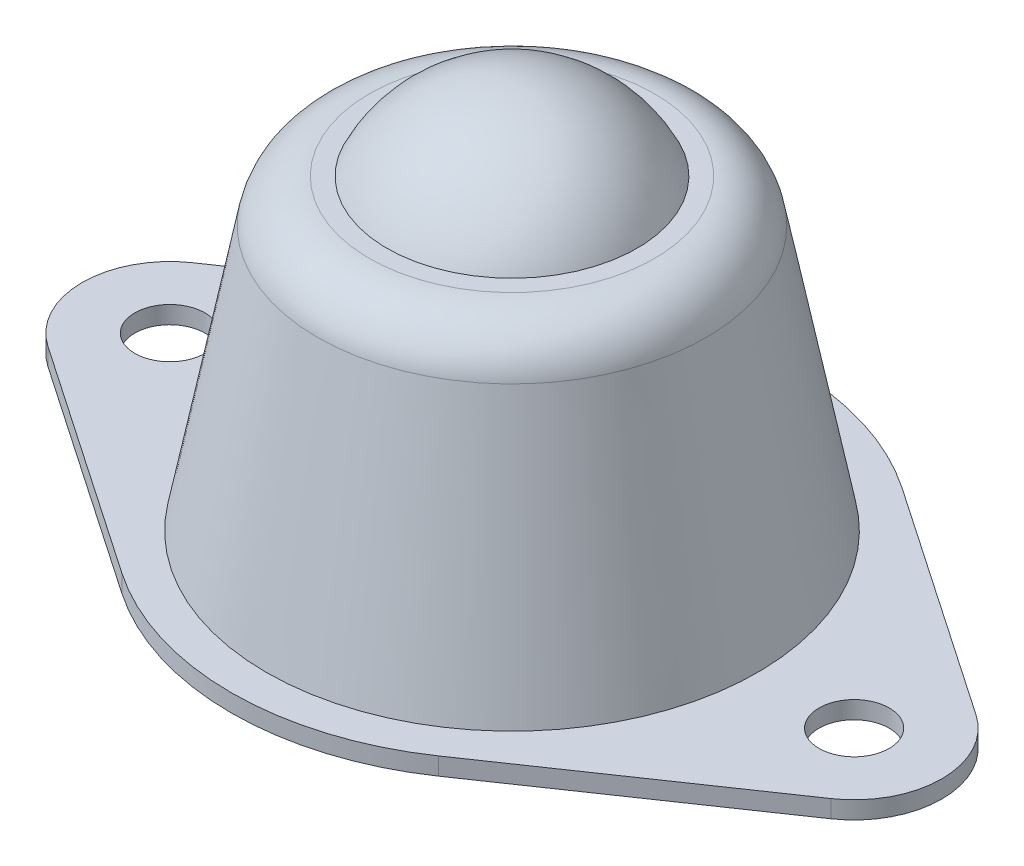
SolidWorks part; units mm, degrees
ref_plane "Front" through (0, 0, 0) normal (0, 0, 1) x (1, 0, 0)
ref_plane "Top" through (0, 0, 0) normal (0, 1, 0) x (1, 0, 0)
ref_plane "Right" through (0, 0, 0) normal (1, 0, 0) x (0, 0, -1)
sketch "草圖1" plane through (0, 0, 0) normal (0, 1, 0) x (1, 0, 0)
  line L0 (-19.5, 0) -> (19.5, 0) construction
  line L1 (-22.3205, 4.1285) -> (-9.0256, 13.2113)
  line L2 (9.0256, 13.2113) -> (22.3205, 4.1285)
  line L3 (-22.3205, -4.1285) -> (-9.0256, -13.2113)
  line L4 (9.0256, -13.2113) -> (22.3205, -4.1285)
  circle A0 centre (19.5, 0) radius 2
  circle A1 centre (-19.5, 0) radius 2
  arc A3 (-22.3205, 4.1285) -> (-22.3205, -4.1285) centre (-19.5, 0) ccw
  arc A4 (22.3205, -4.1285) -> (22.3205, 4.1285) centre (19.5, 0) ccw
  arc A5 (-9.0256, -13.2113) -> (9.0256, -13.2113) centre (0, 0) ccw
  arc A8 (9.0256, 13.2113) -> (-9.0256, 13.2113) centre (0, 0) ccw
  dimension "D1" = 4
  dimension "D2" = 4
  dimension "D4" = 16
  dimension "D5" = 10
  dimension "D6" = 10
  dimension "D7" = 16
  dimension "D3" = 39
extrude "填料-伸長1" add sketch "草圖1" along normal blind 1
sketch "草圖2" plane through (0, 0, 0) normal (0, 0, 1) x (1, 0, 0)
  line L0 (-14, 1) -> (-11.076, 16.0714)
  line L1 (-22.3205, 1) -> (-9.0256, 1) construction
  line L3 (0, 23) -> (0, 1)
  line L4 (9.0256, 1) -> (-9.0256, 1) construction
  line L5 (0, 1) -> (-14, 1)
  line L6 (-7.1309, 18.5) -> (-8.1309, 18.5)
  arc A1 (-7.1309, 18.5) -> (0, 23) centre (0, 15.1) cw
  arc A2 (-8.1309, 18.5) -> (-11.076, 16.0714) centre (-8.1309, 15.5) ccw
  dimension "D1" = 7.9
  dimension "D4" = 4.5
  dimension "D5" = 3
  dimension "D2" = 22
  dimension "D3" = 14
  dimension "D6" = 1
revolve "旋轉1" add sketch "草圖2" angle 360 about L3
